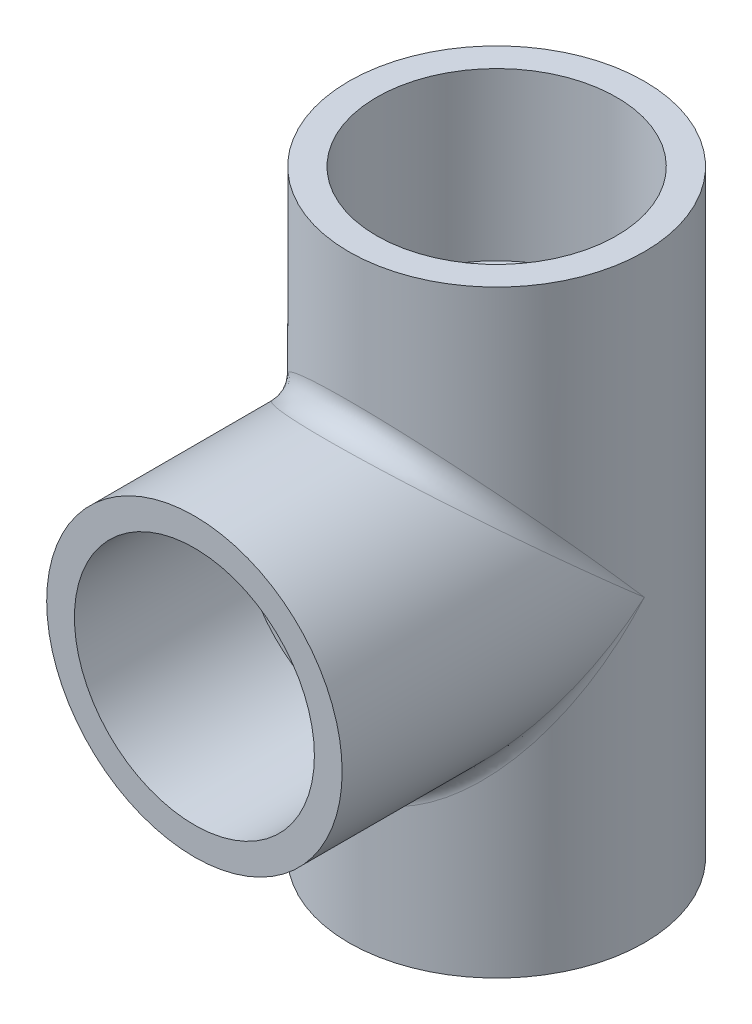
SolidWorks part; units mm, degrees
ref_plane "前视基准面" through (0, 0, 0) normal (0, 0, 1) x (1, 0, 0)
ref_plane "上视基准面" through (0, 0, 0) normal (0, 1, 0) x (1, 0, 0)
ref_plane "右视基准面" through (0, 0, 0) normal (1, 0, 0) x (0, 0, -1)
other "Configuration Table"
sketch "草图1" plane through (0, 0, 0) normal (0, 1, 0) x (1, 0, 0)
  circle A14 centre (0, 0) radius 19.7
  circle A15 centre (0, 0) radius 16
  circle A16 centre (0, 0) radius 13.6
  dimension "D3" = 2.4
  dimension "D1" = 32
  dimension "D2" = 3.7
extrude "凸台-拉伸1" add sketch "草图1" along normal mid plane 79.8 contours A14 | A16
sketch "草图2" plane through (0, 0, 0) normal (0, 0, 1) x (1, 0, 0)
  circle A0 centre (0, 0) radius 16
  circle A1 centre (0, 0) radius 19.7
  circle A2 centre (0, 0) radius 13.6
  dimension "D1" = 32
  dimension "D2" = 2.4
  dimension "D3" = 3.7
extrude "凸台-拉伸2" add sketch "草图2" along normal blind 40.3 contours A1 | A2
ref_plane "基准面1" through (0, 0, -19.7) normal (0, 0, -1) x (-1, 0, 0)
extrude "切除-拉伸1" cut sketch "草图2<3>" against normal up to next from surface contours A2 starting at face at (19.7, 0, 40.3)
sketch "草图2<3>" plane through (0, 0, 0) normal (0, 0, 1) x (1, 0, 0) same geometry as "草图2"
extrude "切除-拉伸2" cut sketch "草图1<11>" against normal through all both and the other way through all contours A16
sketch "草图1<11>" plane through (0, 0, 0) normal (0, 1, 0) x (1, 0, 0) same geometry as "草图1"
extrude "切除-拉伸3" cut sketch "草图2<4>" against normal blind 22.2 from surface contours A0 starting at face at (19.7, 0, 40.3)
sketch "草图2<4>" plane through (0, 0, 0) normal (0, 0, 1) x (1, 0, 0) same geometry as "草图2"
extrude "切除-拉伸4" cut sketch "草图1<12>" along normal blind 22.2 from surface contours A15 starting at face at (0, -39.9, 19.7)
sketch "草图1<12>" plane through (0, 0, 0) normal (0, 1, 0) x (1, 0, 0) same geometry as "草图1"
extrude "切除-拉伸5" cut sketch "草图1<13>" against normal blind 22.2 from surface contours A15 starting at face at (0, 39.9, 19.7)
sketch "草图1<13>" plane through (0, 0, 0) normal (0, 1, 0) x (1, 0, 0) same geometry as "草图1"
fillet "圆角1" radius 3 4 edges at (0, -13.6, 13.6) (0, 13.6, 13.6) (0, 19.7, 19.7) (0, -19.7, 19.7)
